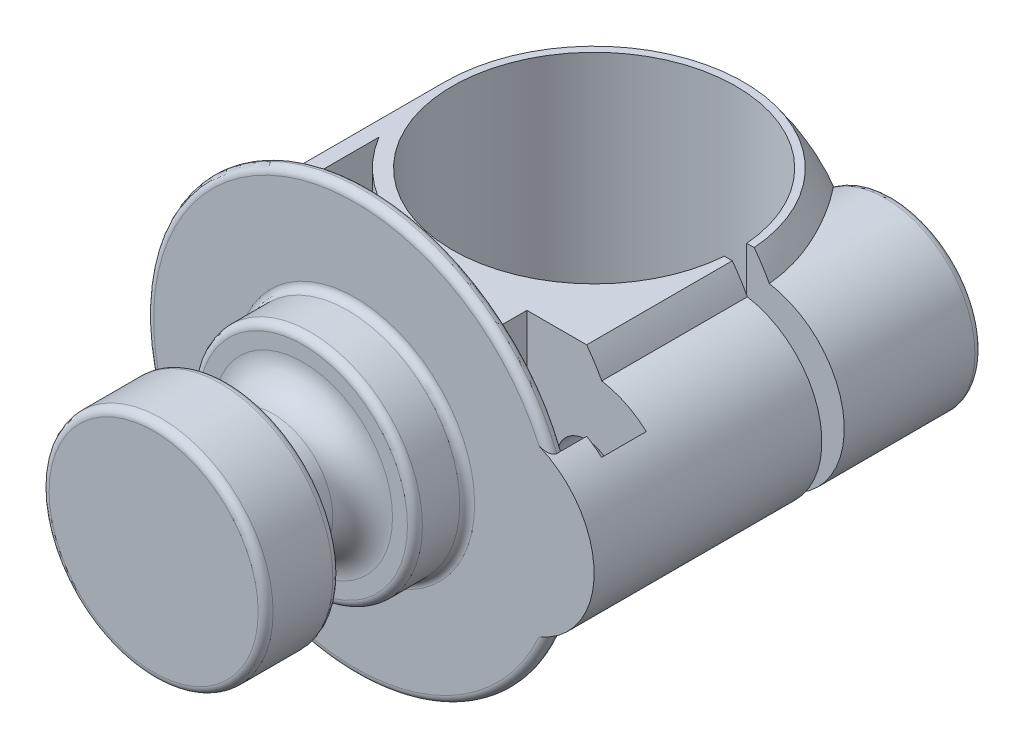
SolidWorks part; units mm, degrees
material "Rubber"
ref_plane "Front Plane" through (0, 0, 0) normal (0, 0, 1) x (1, 0, 0)
ref_plane "Top Plane" through (0, 0, 0) normal (0, 1, 0) x (1, 0, 0)
ref_plane "Right Plane" through (0, 0, 0) normal (1, 0, 0) x (0, 0, -1)
sketch "Sketch1" plane through (0, 0, 0) normal (0, 1, 0) x (1, 0, 0)
  line L0 (-10, 0) -> (-10, -15)
  line L1 (-10, -15) -> (10, -15)
  line L2 (10, -15) -> (10, 0)
  arc A0 (10, 0) -> (-10, 0) centre (0, 0) ccw
extrude "Boss-Extrude1" add sketch "Sketch1" along normal blind 15
sketch "Sketch5" plane through (0, 0, 0) normal (1, 0, 0) x (0, 0, -1)
  line L0 (0, 15) -> (0, -3.6866) construction
  line L1 (0, 15) -> (0, 0) construction
  line L2 (10, 15) -> (10, 0)
  arc A2 (10, 0) -> (10, 15) centre (0, 7.5) ccw
revolve "Revolve1" add sketch "Sketch5" angle 90 about L0 other way angle 90
sketch "Sketch6" plane through (0, 0, 0) normal (0, 0, 1) x (1, 0, 0)
  line L0 (-10, 15) -> (-10, 0)
  line L1 (10, 0) -> (10, 15)
  arc A0 (-10, 15) -> (-10, 0) centre (0, 7.5) ccw
  arc A1 (10, 0) -> (10, 15) centre (0, 7.5) ccw
extrude "Boss-Extrude3" add sketch "Sketch6" along normal blind 15
sketch "Sketch3" plane through (0, 0, 0) normal (0, 0, 1) x (1, 0, 0)
  circle A1 centre (10, 7.5) radius 6
extrude "Boss-Extrude2" add sketch "Sketch3" along normal blind 15 and the other way blind 10
sketch "Sketch7" plane through (0, 0, -10) normal (0, 0, -1) x (-1, 0, 0)
  circle A0 centre (-10, 7.5) radius 2
extrude "Cut-Extrude1" cut sketch "Sketch7" against normal blind 28
sketch "Sketch8" plane through (0, 15, 0) normal (0, 1, 0) x (1, 0, 0)
  circle A0 centre (0, 0) radius 9.5
extrude "Cut-Extrude2" cut sketch "Sketch8" against normal blind 28
sketch "Sketch9" plane through (0, 15, 0) normal (0, 1, 0) x (1, 0, 0)
  line L3 (9.5296, 0.7494) -> (17.5296, 0.7494)
  line L4 (17.5296, 0.7494) -> (17.5296, -0.7494)
  line L5 (17.5296, -0.7494) -> (9.4704, -0.7494)
  line L6 (9.4704, -0.7494) -> (8.4704, -0.7494)
  line L7 (8.4704, -0.7494) -> (8.4704, 0.7494)
  line L8 (8.4704, 0.7494) -> (9.5296, 0.7494)
  circle A0 centre (0, 0) radius 9.5 construction
  point P9 (9.5, 0)
extrude "Cut-Extrude3" cut sketch "Sketch9" against normal blind 28
sketch "Sketch10" plane through (0, 15, 0) normal (0, 1, 0) x (1, 0, 0)
  line L1 (-10, -15) -> (10, -15) construction
  line L2 (-9, -15) -> (-9, -5.4083)
  line L3 (0, -10.5) -> (0, -15)
  line L4 (0, -15) -> (-9, -15)
  line L7 (6, -10.5) -> (14, -10.5)
  line L8 (6, -10.5) -> (6, -13.5)
  line L9 (6, -13.5) -> (7, -13.5)
  line L10 (7, -13.5) -> (7, -15)
  line L11 (7, -15) -> (13, -15)
  line L12 (13, -15) -> (13, -13.5)
  line L13 (13, -13.5) -> (14, -13.5)
  line L14 (14, -13.5) -> (14, -10.5)
  arc A0 (-9, -5.4083) -> (0, -10.5) centre (0, 0) ccw
  point P19 (10, -10.5)
extrude "Cut-Extrude4" cut sketch "Sketch10" against normal blind 11
sketch "Sketch11" plane through (0, 0, 15) normal (0, 0, 1) x (1, 0, 0)
  line L0 (0, 15) -> (0, 0)
  circle A0 centre (0, 7.5) radius 14
  line M1 (0, 4) -> (-9, 4)
  line M2 (-9, 4) -> (-9, 15)
  line M3 (-9, 15) -> (-10, 15)
  arc M4 (-10, 15) -> (-10, 0) centre (0, 7.5) ccw
  line M5 (-10, 0) -> (10, 0)
  arc M6 (10, 0) -> (11.0125, 1.586) centre (0, 7.5) ccw
  arc M7 (11.0125, 1.586) -> (13, 12.6962) centre (10, 7.5) ccw
  line M8 (13, 12.6962) -> (13, 4)
  line M9 (13, 4) -> (7, 4)
  line M10 (7, 4) -> (7, 15)
  line M11 (7, 15) -> (0, 15)
  line M12 (0, 15) -> (0, 4)
extrude "Boss-Extrude4" add sketch "Sketch11" along normal blind 1 contours A0 M8 M7 M6 M5 M4 M3 M2 M1 M12 M11 M10 M9 | A0 L0 M7 M8 M9 M10 M11 M12 M5 M6 | L0 M1 M2 M3 M4 M5 region at (4.9272, 6.7224, 15) region at (-0.1524, 8.2364, 15) region at (-0.1953, 2, 15)
sketch "Sketch12" plane through (0, 0, 15) normal (0, 0, 1) x (1, 0, 0)
  arc A0 (13, 2.3038) -> (13, 12.6962) centre (10, 7.5) ccw
  arc A1 (13, 2.3038) -> (13, 12.6962) centre (0, 7.5) ccw
extrude "Boss-Extrude5" add sketch "Sketch12" along normal blind 1
sketch "Sketch13" plane through (0, 0, 16) normal (0, 0, 1) x (1, 0, 0)
  circle A0 centre (0, 7.5) radius 7.5
extrude "Boss-Extrude6" add sketch "Sketch13" along normal blind 3.5
sketch "Sketch14" plane through (0, 0, 19.5) normal (0, 0, 1) x (1, 0, 0)
  circle A0 centre (0, 7.5) radius 4
extrude "Boss-Extrude7" add sketch "Sketch14" along normal blind 5
sketch "Sketch15" plane through (0, 0, 24.5) normal (0, 0, 1) x (1, 0, 0)
  circle A0 centre (0, 7.5) radius 7.5
extrude "Boss-Extrude8" add sketch "Sketch15" along normal blind 5
fillet "Fillet1" radius 2 2 edges at (4, 7.5, 24.5) (4, 7.5, 19.5)
fillet "Fillet2" radius 0.5 7 edges at (16, 7.5, -10) (-14, 7.5, 15) (-14, 7.5, 16) (7.5, 7.5, 29.5) (7.5, 7.5, 24.5) (7.5, 7.5, 16) (7.5, 7.5, 19.5)
